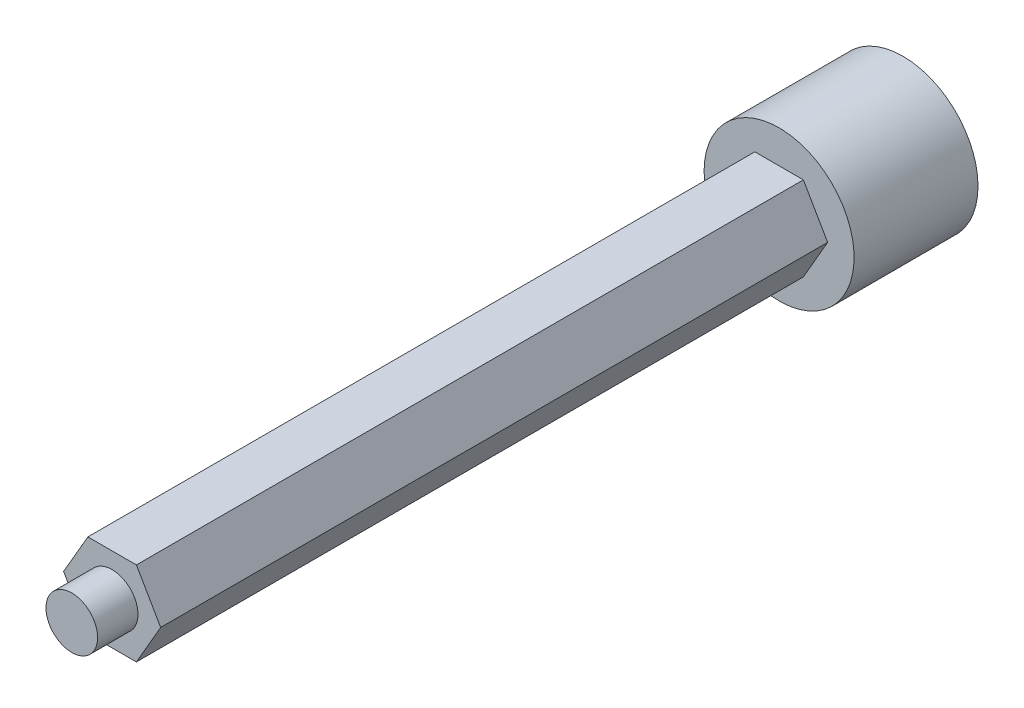
SolidWorks part; units mm, degrees
note: '?' marks a value the reader was unsure of.
material "Nylon 6/10"
ref_plane "Front Plane" through (0, 0, 0) normal (0, 0, 1) x (1, 0, 0)
ref_plane "Top Plane" through (0, 0, 0) normal (0, 1, 0) x (1, 0, 0)
ref_plane "Right Plane" through (0, 0, 0) normal (1, 0, 0) x (0, 0, -1)
ref_axis "Axis1" through (0, 0, 62.6522) along (0, 0, -1)?
ref_plane "Plane5" through (0, 0, 1.6) normal (0, 0, 1) x (1, 0, 0)
sketch "Standoff" plane through (0, 0, 1.6) normal (0, 0, 1) x (1, 0, 0)
  line L1 (3.6662, 0) -> (1.8331, 3.175)
  line L2 (1.8331, 3.175) -> (-1.8331, 3.175)
  line L3 (-1.8331, 3.175) -> (-3.6662, 0)
  line L4 (-3.6662, 0) -> (-1.8331, -3.175)
  line L5 (-1.8331, -3.175) -> (1.8331, -3.175)
  line L6 (1.8331, -3.175) -> (3.6662, 0)
  circle A0 centre (0, 0) radius 3.175 construction
  circle A1 centre (0, 0) radius 3.6662 construction
  dimension "D1" = 6.35
extrude "Hex extrude" add sketch "Standoff" along normal up to surface (58.145 mm away)
ref_plane "Plane4" through (0, 0, 59.745) normal (0, 0, 1) x (1, 0, 0)
sketch "Sketch3" plane through (0, 0, 1.6) normal (0, 0, 1) x (1, 0, 0)
  circle A0 centre (0, 0) radius 2
  dimension "D1" = 4
extrude "Thru hole" [suppressed] cut sketch "Sketch3" along normal up to next
sketch "Set Grub Screw" plane through (0, 3.175, 0) normal (0, 1, 0) x (1, 0, 0)
  line L0 (0, 0) -> (0, -59.745) construction
  line L1 (1.8331, -59.745) -> (-1.8331, -59.745) construction
  circle A0 centre (0, -5) radius 1.5
  dimension "D1" = 3
  dimension "D2" = 5
extrude "Grub screw hole" [suppressed] cut sketch "Set Grub Screw" against normal through all
thread "Grub screw thread" [suppressed] pitch 0.5 start angle 0, offset 0, length 0, pitch 0.5, diameter 3
ref_plane "Plane2" through (-1.5, 3.175, 5) normal (0, 0, 1) x (-1, 0, 0)
sketch "Thread Profile2" plane through (-1.5, 3.175, 5) normal (0, 0, 1) x (-1, 0, 0)
  line L0 (0, 0) -> (0, 0.5) construction
  line L1 (0, 0) -> (0.2706, 0.1562)
  line L2 (0.2706, 0.1562) -> (0.2706, 0.2187)
  line L3 (0.2706, 0.2187) -> (0, 0.375)
  line L4 (0.2706, 0.1875) -> (0, 0.1875) construction
  line L11 (0, 0) -> (0, 0.375)
  point P2 (0, 0)
  dimension "Pitch" = 0.5
  dimension "Profile_Angle" = 60
  dimension "Profile_Land" = 0.0625
  dimension "Profile_Height" = 0.2706
sketch "Sketch11" plane through (0, 0, 59.745) normal (0, 0, 1) x (1, 0, 0)
  circle A0 centre (0, 0) radius 1.9844
  dimension "D1" = 3.9688
extrude "Cut-Extrude3" [suppressed] cut sketch "Sketch11" against normal blind 20
sketch "Cotter Pin" plane through (0, 3.175, 0) normal (0, 1, 0) x (1, 0, 0)
  line L0 (0, -31.6) -> (-1.8331, -31.6) construction
  line L1 (-1.8331, -59.745) -> (-1.8331, -1.6) construction
  line L2 (0, 0) -> (0, -59.745) construction
  line L3 (1.8331, -1.6) -> (-1.8331, -1.6) construction
  circle A0 centre (0, -32.3) radius 0.7
  dimension "D1" = 1.4
  dimension "D2" = 30
extrude "Cotter pin hole" [suppressed] cut sketch "Cotter Pin" against normal through all
thread "#8 thread" [suppressed] pitch 0.7937 start angle 0, offset 0, length 10, pitch 0.7937, diameter 3.9688
ref_plane "Plane3" through (-1.9844, 0, 43.6) normal (0, -1, 0) x (-1, 0, 0)
sketch "Thread Profile3" plane through (-1.9844, 0, 43.6) normal (0, -1, 0) x (-1, 0, 0)
  line L0 (0, 0) -> (0, 0.7937) construction
  line L1 (0, 0) -> (0.4296, 0.248)
  line L2 (0.4296, 0.248) -> (0.4296, 0.3473)
  line L3 (0.4296, 0.3473) -> (0, 0.5953)
  line L4 (0.4296, 0.2977) -> (0, 0.2977) construction
  line L11 (0, 0) -> (0, 0.5953)
  point P2 (0, 0)
  dimension "Pitch" = 0.7937
  dimension "Profile_Angle" = 60
  dimension "Profile_Land" = 0.0992
  dimension "Profile_Height" = 0.4296
sketch "Sketch12" plane through (0, 0, 1.6) normal (0, 0, 1) x (1, 0, 0)
  line L0 (-1.3229, 1.5) -> (1.3229, 1.5) construction
  line L1 (-1.3229, 1.5) -> (1.3229, 1.5) construction
  line L2 (1.3947, 1.57) -> (-1.3947, 1.57)
  arc A0 (-1.3229, 1.5) -> (1.3229, 1.5) centre (0, 0) ccw construction
  arc A1 (-1.3229, 1.5) -> (1.3229, 1.5) centre (0, 0) ccw construction
  arc A2 (-1.3947, 1.57) -> (1.3947, 1.57) centre (0, 0) ccw
  dimension "D1" = 0.1
  dimension "D2" = 0.07
extrude "Motor shaft" cut sketch "Sketch12" along normal blind 9
sketch "Sketch15" plane through (0, 0, 0) normal (0, 0, 1) x (1, 0, 0)
  line L0 (-3.6662, 0) -> (-5.6662, 0) construction
  circle A0 centre (0, 0) radius 5.6662
  circle A2 centre (0, 0) radius 2.1 construction
  circle A3 centre (0, 0) radius 2.2
  dimension "D2" = 0.1
  dimension "D1" = 2
extrude "Motor spacer" add sketch "Sketch15" along normal up to surface (1.6 mm away) up to plane "Plane5"
sketch "Sketch16" plane through (0, 0, 1.6) normal (0, 0, 1) x (1, 0, 0)
  line L6 (3.6662, 0) -> (1.8331, 3.175)
  line L7 (1.8331, 3.175) -> (-1.8331, 3.175)
  line L8 (-1.8331, 3.175) -> (-3.6662, 0)
  line L9 (-3.6662, 0) -> (-1.8331, -3.175)
  line L10 (-1.8331, -3.175) -> (1.8331, -3.175)
  line L11 (1.8331, -3.175) -> (3.6662, 0)
  line L12 (3.6662, 0) -> (1.8331, 3.175)
  line L13 (1.8331, 3.175) -> (-1.8331, 3.175)
  line L14 (-1.8331, 3.175) -> (-3.6662, 0)
  line L15 (-3.6662, 0) -> (-1.8331, -3.175)
  line L16 (-1.8331, -3.175) -> (1.8331, -3.175)
  line L17 (1.8331, -3.175) -> (3.6662, 0)
  circle A2 centre (0, 0) radius 5.6662 construction
  circle A3 centre (0, 0) radius 5.6662
  dimension "D1" = 0
extrude "Hub inner spacer" add sketch "Sketch16" along normal up to surface (7.76 mm away)
sketch "Sketch14" plane through (0, 0, 59.745) normal (0, 0, 1) x (1, 0, 0)
  circle A2 centre (0, 0) radius 1.95
  point P1 (-4.5439, -0.2478)
  point P2 (-6.734, -0.4506)
  dimension "D1" = 3.9
extrude "Bearing" add sketch "Sketch14" along normal up to surface (3.048 mm away)
equation "\"D1@Sketch11\"=25.4*5/32"
